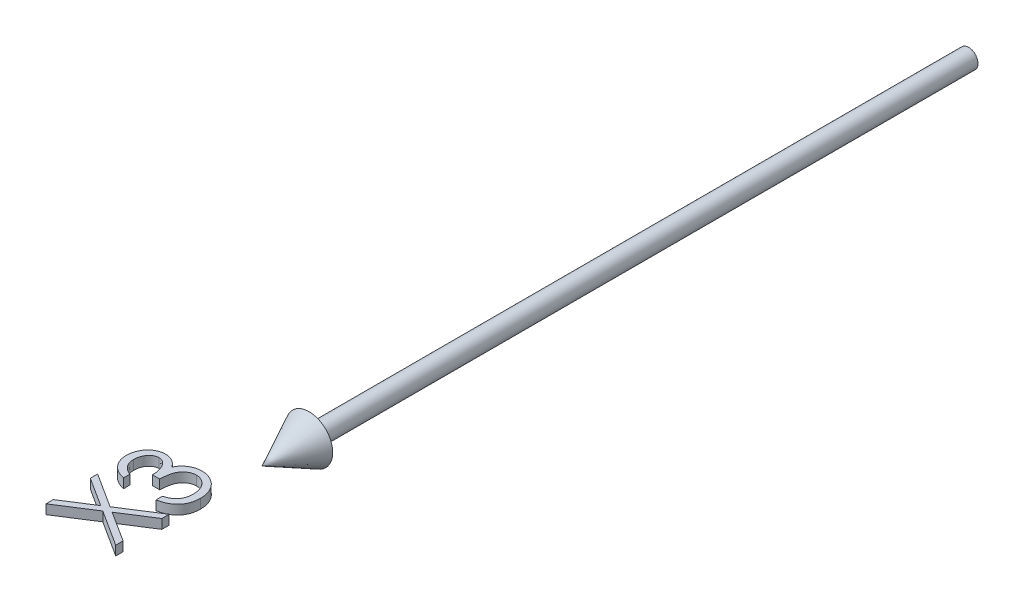
SolidWorks part; units mm, degrees
ref_plane "Front Plane" through (0, 0, 0) normal (0, 0, 1) x (1, 0, 0)
ref_plane "Top Plane" through (0, 0, 0) normal (0, 1, 0) x (1, 0, 0)
ref_plane "Right Plane" through (0, 0, 0) normal (1, 0, 0) x (0, 0, -1)
sketch "Sketch2" plane through (0, 0, 0) normal (0, 1, 0) x (1, 0, 0)
  line L0 (0, 41.95) -> (0, -114.4521) construction
  line L1 (-36.8894, 0) -> (41.4965, 0) construction
  line L2 (0, -150) -> (5, -140)
  line L3 (5, -140) -> (2, -140)
  line L4 (2, -140) -> (2, 0)
  line L5 (2, 0) -> (0, 0)
  line L6 (0, 0) -> (0, -150)
  dimension "D1" = 150
  dimension "D2" = 2
  dimension "D3" = 10
  dimension "D4" = 5
revolve "Revolve1" add sketch "Sketch2" angle 360 about L0
sketch "Sketch3" plane through (0, 0, 0) normal (0, 1, 0) x (1, 0, 0)
  line L0 (0, -157.5) -> (0, -279.9745) construction
  line L1 (-18.6107, 0) -> (18.3141, 0) construction
  text T0 "X3" font "Century Gothic" height 15
  point P3 (0, -279.9745)
  point P4 (-2.5, -155.7304)
  dimension "D1" = 157.5
extrude "Boss-Extrude1" add sketch "Sketch3" against normal blind 1 and the other way blind 1 separate body
equation "\"D1@Sketch2\"=\"frame_arrow_length\""
equation "\"D2@Sketch2\"=\"frame_arrow_odA\"/2"
equation "\"D4@Sketch2\"=\"frame_arrow_head_od\""
equation "\"D3@Sketch2\"=\"frame_arrow_head_length\""
equation "\"frame_arrow_length\"=150"
equation "\"frame_arrow_head_length\"=10"
equation "\"frame_arrow_head_od\"=5"
equation "\"frame_arrow_odA\"=4"
equation "\"D1@Sketch3\"=\"frame_arrow_length\"*1.05"
